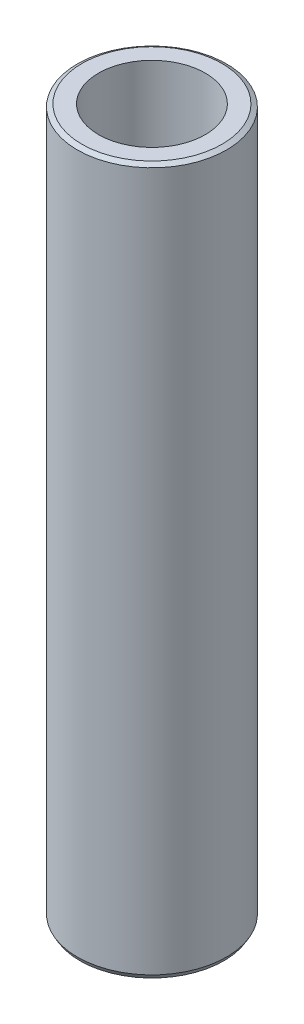
SolidWorks part; units mm, degrees
ref_plane "Front Plane" through (0, 0, 0) normal (0, 0, 1) x (1, 0, 0)
ref_plane "Top Plane" through (0, 0, 0) normal (0, 1, 0) x (1, 0, 0)
ref_plane "Right Plane" through (0, 0, 0) normal (1, 0, 0) x (0, 0, -1)
sketch "Sketch1" plane through (0, 0, 0) normal (0, 1, 0) x (1, 0, 0)
  circle A0 centre (0, 0) radius 25
  dimension "SHAFT_OD" = 50
extrude "Boss-Extrude1" add sketch "Sketch1" along normal blind 236.6287
sketch "Sketch2" plane through (0, 0, 0) normal (0, 1, 0) x (1, 0, 0)
  circle A0 centre (0, 0) radius 17.8828
  dimension "BORE_D" = 35.7656
extrude "Cut-Extrude1" cut sketch "Sketch2" along normal through all
chamfer "Chamfer1" distance 0.8842 angle 60 2 edges at (0, 236.6287, 25) (0, 0, 25) first distance on face at (0, 236.6287, 25) first distance on face at (0, 0, 17.8828)
